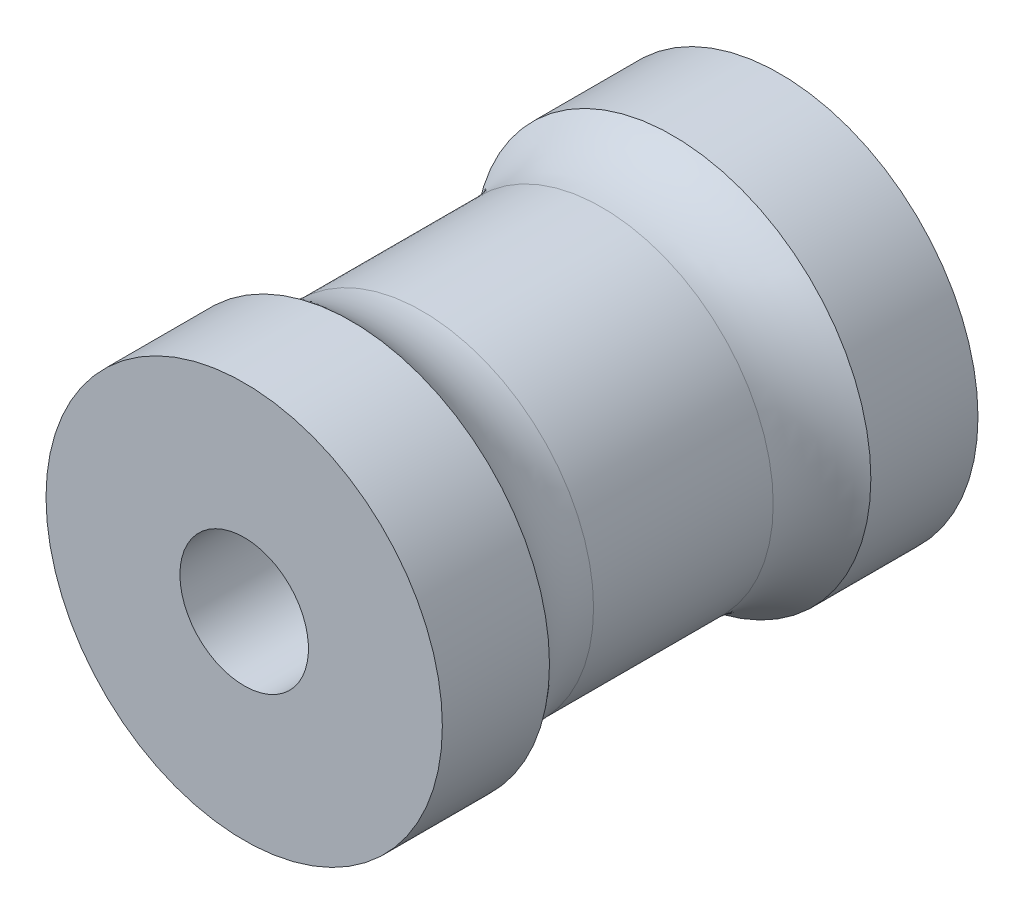
SolidWorks part; units mm, degrees
ref_plane "Front Plane" through (0, 0, 0) normal (1, 0, 0) x (0, 1, 0)
ref_plane "Top Plane" through (0, 0, 0) normal (0, 0, 1) x (0, 1, 0)
ref_plane "Right Plane" through (0, 0, 0) normal (0, 1, 0) x (-1, 0, 0)
sketch "Sketch2" plane through (0, 0, 0) normal (1, 0, 0) x (0, 1, 0)
  line L0 (0, 0) -> (0, 6.35) construction
  line L1 (0, 0) -> (4.699, 0) construction
  line L2 (4.699, 0) -> (1.524, 0)
  line L3 (4.699, 0) -> (4.699, 2.54)
  line L4 (0, 6.35) -> (4.699, 6.35) construction
  line L5 (4.699, 6.35) -> (4.699, 0) construction
  line L6 (4.699, 2.54) -> (4.064, 2.54)
  line L7 (4.064, 2.54) -> (4.064, 10.16)
  line L8 (1.524, 0) -> (1.524, 12.7)
  line L9 (1.524, 6.35) -> (4.064, 6.35) construction
  line L10 (4.699, 12.7) -> (1.524, 12.7)
  line L11 (4.699, 12.7) -> (4.699, 10.16)
  line L12 (4.699, 10.16) -> (4.064, 10.16)
  dimension "D1" = 1.524
  dimension "D2" = 3.175
  dimension "D3" = 6.35
  dimension "D4" = 2.54
  dimension "D5" = 2.54
revolve "Revolve1" add sketch "Sketch2" angle 360 about L0
fillet "Fillet1" radius 2.54 2 edges at (-4.064, 0, 2.54) (-4.064, 0, 10.16)
